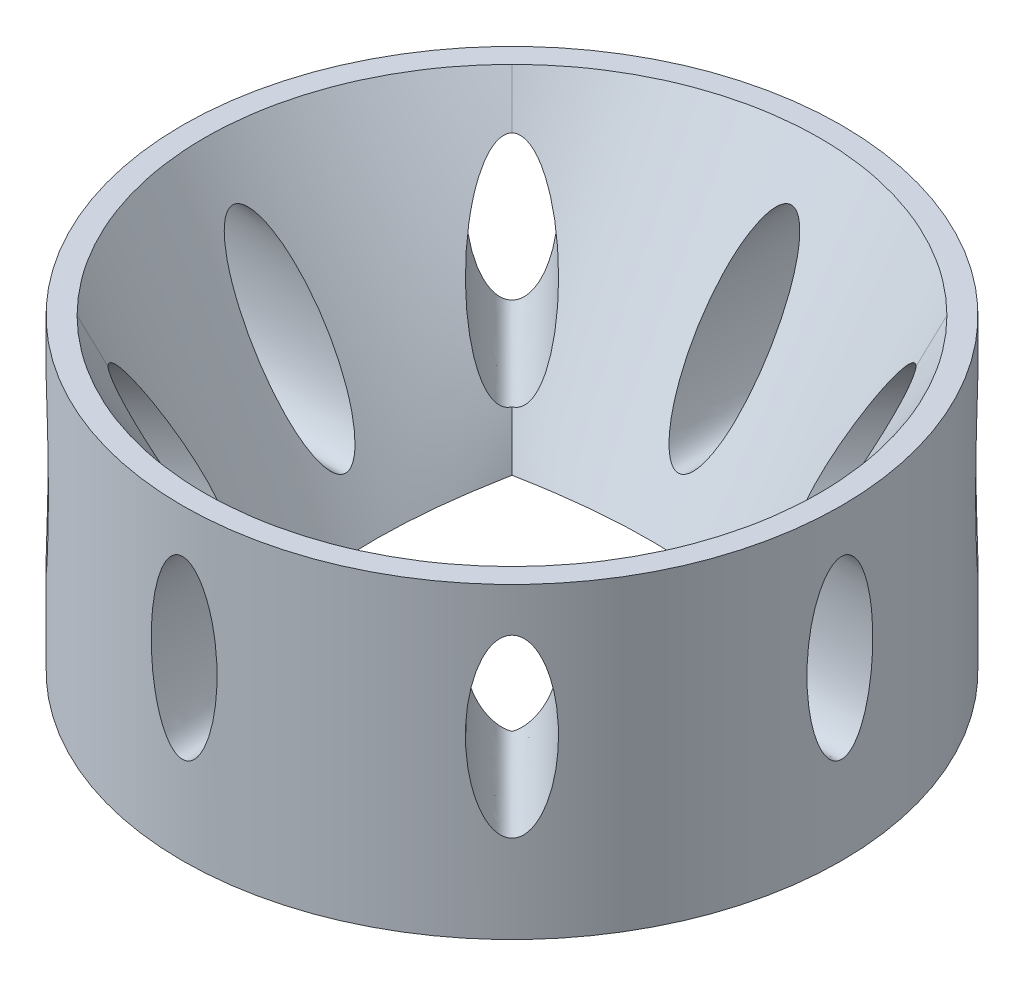
SolidWorks part; units mm, degrees
ref_plane "Спереди XY" through (0, 0, 0) normal (0, 0, 1) x (1, 0, 0)
ref_plane "Сверху XZ" through (0, 0, 0) normal (0, 1, 0) x (1, 0, 0)
ref_plane "Справа ZY" through (0, 0, 0) normal (1, 0, 0) x (0, 0, -1)
sketch "Эскиз5" plane through (0, 0, 0) normal (0, 1, 0) x (1, 0, 0)
  circle A0 centre (0, 0) radius 7.5
  dimension "D1" = 15
extrude "Бобышка-Вытянуть1" add sketch "Эскиз5" along normal blind 7
sketch "Эскиз7" plane through (0, 7, 0) normal (0, 1, 0) x (1, 0, 0)
  circle A0 centre (0, 0) radius 7
  dimension "D1" = 14
sketch "Эскиз8" plane through (0, 0, 0) normal (0, -1, 0) x (1, 0, 0)
  line L1 (-2.5, -2.5) -> (2.5, -2.5)
  line L2 (-2.5, -2.5) -> (-2.5, 2.5)
  line L3 (-2.5, 2.5) -> (2.5, 2.5)
  line L4 (2.5, -2.5) -> (2.5, 2.5)
  line L5 (-2.5, -2.5) -> (2.5, 2.5) construction
  line L6 (-2.5, 2.5) -> (2.5, -2.5) construction
  point P0 (0, 0)
  dimension "D1" = 5
  dimension "D2" = 5
loft "Вырез-По сечениям4" cut profiles "Эскиз7", "Эскиз8"
sketch "Эскиз13" plane through (0, 0, 0) normal (1, 0, 0) x (0, 0, -1)
  ellipse E0 centre (0, 4) end of major axis (0, 2) minor radius 0.75
  point P1 (0, 0)
  dimension "D1" = 4
  dimension "D2" = 1.5
  dimension "D3" = 4
extrude "Вырез-Вытянуть5" cut sketch "Эскиз13" against normal through all
ref_axis "Ось1" through (0, 7.3513, 0) along (0, -1, 0)
pattern_circular "Круговой массив1" count 8 over 360 about axis through (0, 7.3513, 0) along (0, -1, 0) of "Вырез-Вытянуть5"
sketch "Эскиз14" plane through (0, 0, 0) normal (0, -1, 0) x (1, 0, 0)
  circle A0 centre (0, 0) radius 6
  dimension "D1" = 12
extrude "Вырез-Вытянуть6" cut sketch "Эскиз14" against normal blind 1
